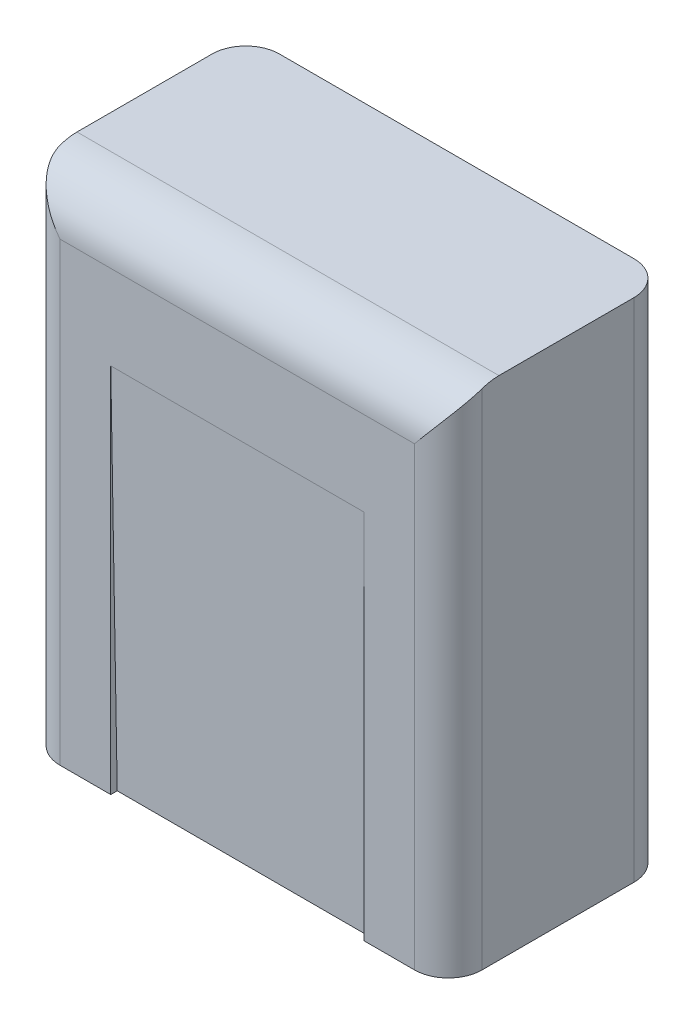
SolidWorks part; units mm, degrees
material "K110"
ref_plane "Front Plane" through (0, 0, 0) normal (0, 0, 1) x (1, 0, 0)
ref_plane "Top Plane" through (0, 0, 0) normal (0, 1, 0) x (1, 0, 0)
ref_plane "Right Plane" through (0, 0, 0) normal (1, 0, 0) x (0, 0, -1)
sketch "Sketch1" plane through (0, 0, 0) normal (0, 1, 0) x (1, 0, 0)
  line L1 (-12.5, -6.5) -> (12.5, -6.5)
  line L2 (-12.5, -6.5) -> (-12.5, 6.5)
  line L3 (-12.5, 6.5) -> (12.5, 6.5)
  line L4 (12.5, -6.5) -> (12.5, 6.5)
  line L5 (-12.5, -6.5) -> (12.5, 6.5) construction
  line L6 (-12.5, 6.5) -> (12.5, -6.5) construction
  point P0 (0, 0)
  dimension "D1" = 13
  dimension "D2" = 25
extrude "Boss-Extrude1" add sketch "Sketch1" against normal blind 30
fillet "Fillet1" radius 2 4 edges at (-12.5, -15, -6.5) (-12.5, -15, 6.5) (12.5, -15, -6.5) (12.5, -15, 6.5)
fillet "Fillet2" radius 3 1 edges at (0, 0, 6.5) tangent propagation no
hole_wizard "M6 Tapped Hole1" positions "Sketch4" profile "Sketch3" tap size "M6" standard "ISO"
sketch "Sketch4" plane through (0, -30, 0) normal (0, -1, 0) x (-1, 0, 0)
  line L0 (-12.5, -4.5) -> (-12.5, 4.5) construction
  line L1 (12.5, 4.5) -> (12.5, -4.5) construction
  point P0 (-5, 0)
  point P2 (5, 0)
  point P9 (0, 0)
  dimension "D1" = 7.5
  dimension "D2" = 7.5
sketch "Sketch3" plane through (5, -30, 0) normal (1, 0, 0) x (0, 0, -1)
  line L0 (0, 0) -> (0, 18.5022)
  line L1 (0, 18.5022) -> (2.5, 17)
  line L2 (2.5, 17) -> (2.5, 0.525)
  line L3 (2.5, 0.525) -> (3.025, 0)
  line L5 (3.025, 0) -> (0, 0)
  line L6 (-2.5, 0.525) -> (-3.025, 0) construction
  line L10 (0, 18.5022) -> (-2.5, 17) construction
  line L11 (0, -6.35) -> (0, 107.95) construction
  dimension "Tap Drill Dia." = 5
  dimension "Tap Drill Depth" = 17
  dimension "Near C'Sink Dia." = 6.05
  dimension "Near C'Sink Angle" = 90
  dimension "Drill Angle" = 118
cosmetic thread "Hole Thread1" parameters "D1"=12, "D2"=6
cosmetic thread "Hole Thread2" parameters "D1"=12, "D2"=6
sketch "Sketch5" plane through (0, 0, 0) normal (1, 0, 0) x (0, 0, -1)
  line L4 (-6.5, -8) -> (-6.116, -30)
  line L5 (-6.5, -30) -> (-6.5, -3) construction
  line L6 (-6.5, -30) -> (-4.5, -30) construction
  line L7 (-6.116, -30) -> (-6.5, -30)
  line L8 (-6.5, -30) -> (-6.5, -8)
  dimension "D1" = 5
  dimension "D2" = 1
extrude "Cut-Extrude1" cut sketch "Sketch5" against normal mid plane 15
